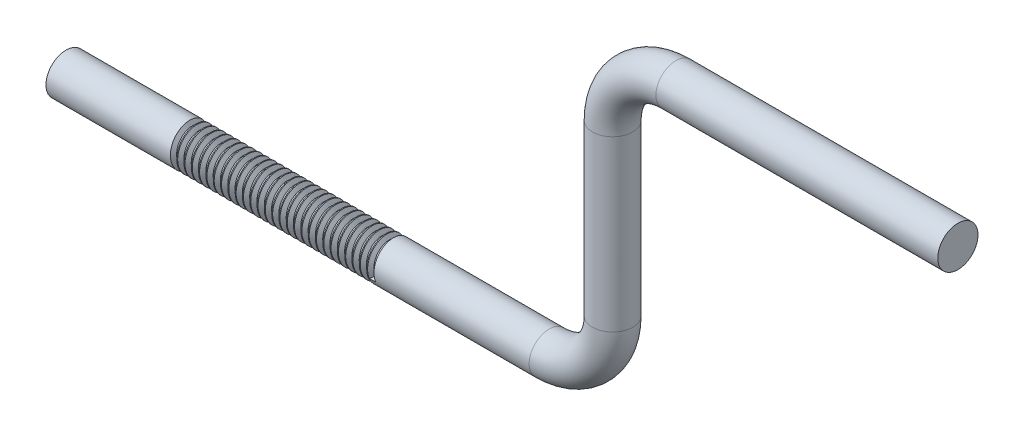
SolidWorks part; units mm, degrees
ref_plane "Front" through (0, 0, 0) normal (0, 0, 1) x (1, 0, 0)
ref_plane "Top" through (0, 0, 0) normal (0, 1, 0) x (1, 0, 0)
ref_plane "Right" through (0, 0, 0) normal (1, 0, 0) x (0, 0, -1)
sketch "Sketch1" plane through (0, 0, 0) normal (0, 0, 1) x (1, 0, 0)
  line L0 (-20.5632, 0) -> (24.4368, 0)
  line L1 (55, 0) -> (-55, 0) construction
  line L2 (32.3103, 7.8735) -> (32.3103, 28.8735)
  line L3 (40.1838, 36.747) -> (75.1838, 36.747)
  arc A0 (24.4368, 0) -> (32.3103, 7.8735) centre (24.4368, 7.8735) ccw
  arc A1 (40.1838, 36.747) -> (32.3103, 28.8735) centre (40.1838, 28.8735) ccw
  point P8 (24.4368, 0)
  point P12 (32.3103, 28.8735)
  dimension "D3" = 15.747
  dimension "D4" = 15.747
  dimension "D1" = 45
  dimension "D2" = 35
  dimension "D5" = 21
ref_plane "Plane1" through (-20.5632, 0, 0) normal (1, 0, 0) x (0, 0, -1)
sketch "Sketch3" plane through (-20.5632, 0, 0) normal (1, 0, 0) x (0, 0, -1)
  circle A0 centre (0, 0) radius 2.5
  point P0 (0, 0)
sweep "Sweep1" add profiles "Sketch3" path "Sketch1"
sketch "Sketch4" plane through (0, 0, 0) normal (0, 0, 1) x (1, 0, 0)
  line L1 (75.1838, 39.247) -> (40.1838, 39.247) construction
  line L3 (75.1838, 39.247) -> (40.1838, 39.247)
  line L4 (40.1838, 39.247) -> (40.1838, 45.747)
  line L5 (50.4866, 45.747) -> (73.4428, 45.747)
  line L6 (78.4428, 40.747) -> (78.4428, 39.247)
  line L7 (75.1838, 39.247) -> (40.1838, 39.247)
  line L8 (75.1838, 39.247) -> (75.1838, 36.747)
  line L10 (75.1838, 34.247) -> (75.1838, 39.247) construction
  line L12 (75.1838, 36.747) -> (78.4428, 36.747)
  line L14 (78.4428, 36.747) -> (78.4428, 39.247)
  line L16 (40.1838, 36.747) -> (78.4428, 36.747) construction
  line L17 (40.1838, 39.247) -> (40.1838, 34.247) construction
  arc A0 (46.4512, 47.7948) -> (40.1838, 45.747) centre (43.652, 45.747) ccw
  arc A2 (78.4428, 40.747) -> (73.4428, 45.747) centre (73.4428, 40.747) ccw
  arc A3 (50.4866, 45.747) -> (46.4512, 47.7948) centre (50.4866, 50.747) cw
  point P15 (47.1203, 45.747)
  dimension "D2" = 5
  dimension "D3" = 5
  dimension "D1" = 6.5
ref_plane "Plane2" through (-5.5632, 0, 0) normal (1, 0, 0) x (0, 0, -1)
sketch "Sketch5" plane through (-5.5632, 0, 0) normal (1, 0, 0) x (0, 0, -1)
  circle A0 centre (0, 0) radius 2.5 construction
  circle A1 centre (0, 0) radius 2.5
thread "Thread2" pitch 0.9071 method cut profile "Thread Profile2" start angle 0, offset 0, length 25, pitch 0.9071, diameter 5
ref_plane "Plane4" through (-20.5632, 0, -2.5) normal (0, -1, 0) x (0, 0, -1)
sketch "Thread Profile2" plane through (-20.5632, 0, -2.5) normal (0, -1, 0) x (0, 0, -1)
  line L0 (0, 0) -> (0, 0.9071) construction
  line L11 (0, 0) -> (0, 0.7937)
  line L12 (0, 0.7937) -> (-0.491, 0.5103)
  line L13 (-0.491, 0.5103) -> (-0.491, 0.2835)
  line L15 (-0.491, 0.2835) -> (0, 0)
  line L17 (-0.491, 0.3969) -> (0, 0.3969) construction
  point P2 (0, 0)
  dimension "Pitch" = 0.9071
  dimension "Profile_Angle" = 60
  dimension "Profile_Land" = 0.2268
  dimension "Profile_Height" = 0.491
sketch "Sketch17" plane through (-20.5632, 0, 0) normal (1, 0, 0) x (0, 0, -1)
  circle A0 centre (0, 0) radius 2.5 construction
  circle A1 centre (0, 0) radius 2.5
extrude "Boss-Extrude1" add sketch "Sketch17" against normal blind 15
